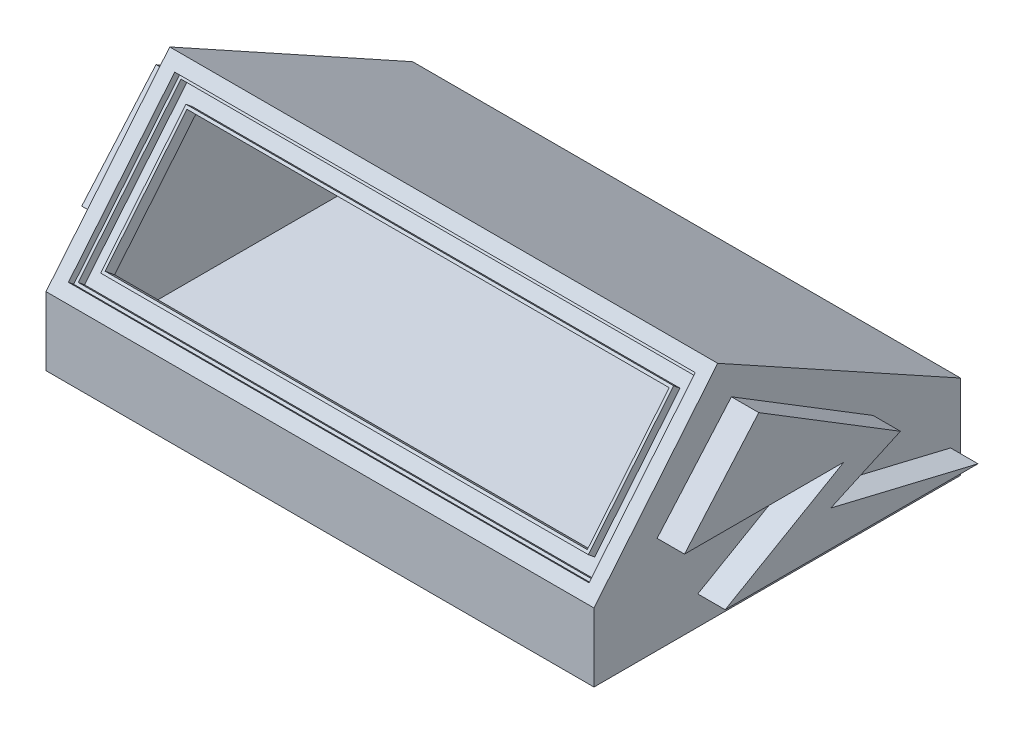
SolidWorks part; units mm, degrees
ref_plane "Front Plane" through (0, 0, 0) normal (0, 0, 1) x (1, 0, 0)
ref_plane "Top Plane" through (0, 0, 0) normal (0, 1, 0) x (1, 0, 0)
ref_plane "Right Plane" through (0, 0, 0) normal (1, 0, 0) x (0, 0, -1)
sketch "Sketch1" plane through (0, 0, 0) normal (1, 0, 0) x (0, 0, -1)
  line L0 (42.0739, 65.0414) -> (130.7147, 16.0632)
  line L5 (130.7147, 16.0632) -> (130.7147, -14.7157)
  line L6 (-4.3853, -14.7157) -> (164.6147, -14.7157) construction
  line L7 (130.7147, -14.7157) -> (-3.084, -14.7157)
  line L13 (-3.084, 10.2843) -> (-3.084, -14.7157)
  line L14 (-3.084, 10.2843) -> (42.0739, 65.0414)
  point P0 (0, 0)
extrude "Boss-Extrude2" add sketch "Sketch1" along normal mid plane 200
sketch "Sketch6" plane through (-100, 0, 0) normal (-1, 0, 0) x (0, 0, 1)
  line L0 (-99.8291, 20.1495) -> (-46.9657, 52.6082)
  line L5 (-46.9657, 52.6082) -> (-18.8617, 20.2843) construction
  line L6 (-99.8291, 20.1495) -> (-46.9657, 52.6082) construction
  line L7 (-46.9657, 52.6082) -> (-18.8617, 20.2843)
  line L8 (-18.8617, 20.2843) -> (-76.2365, 20.2843)
  line L9 (-76.2365, 20.2843) -> (-32.9353, -4.7157)
  line L10 (-32.9353, -4.7157) -> (-131.3101, -4.7157)
  line L11 (-131.3101, -4.7157) -> (-74.8772, 8.8048) construction
  line L12 (-32.9353, -4.7157) -> (-131.3101, -4.7157) construction
  line L13 (-131.3101, -4.7157) -> (-74.8772, 8.8048)
  line L14 (-74.8772, 8.8048) -> (-99.8291, 20.1495) construction
  line L15 (-74.8772, 8.8048) -> (-99.8291, 20.1495)
  line L16 (-73.3455, 8.6576) -> (-98.7661, 20.2154)
  line L17 (-98.7661, 20.2154) -> (-47.0651, 51.9604)
  line L18 (-47.0651, 51.9604) -> (-19.959, 20.7843)
  line L19 (-19.959, 20.7843) -> (-78.1025, 20.7843)
  line L20 (-78.1025, 20.7843) -> (-34.8013, -4.2157)
  line L21 (-34.8013, -4.2157) -> (-127.0772, -4.2157)
  line L22 (-127.0772, -4.2157) -> (-73.3455, 8.6576)
  point P0 (-63.3626, 19.2467)
  dimension "D1" = 0.5
extrude "Boss-Extrude4" add sketch "Sketch6" along normal blind 10 contours L16 L17 L18 L19 L20 L21 L22
mirror "Mirror1" about plane through (0, 0, 0) normal (1, 0, 0) of "Boss-Extrude4"
sketch "Sketch3" plane through (0, 0, 0) normal (1, 0, 0) x (0, 0, -1)
  line L10 (43.7761, 56.1034) -> (3.916, 7.7702)
  line L11 (3.916, 7.7702) -> (3.916, -7.7157)
  line L12 (3.916, -7.7157) -> (123.7147, -7.7157)
  line L13 (123.7147, -7.7157) -> (123.7147, 11.9335)
  line L14 (123.7147, 11.9335) -> (43.7761, 56.1034)
  line L15 (43.7761, 56.1034) -> (3.916, 7.7702)
  line L16 (3.916, 7.7702) -> (3.916, -7.7157)
  line L17 (3.916, -7.7157) -> (123.7147, -7.7157)
  line L18 (123.7147, -7.7157) -> (123.7147, 11.9335)
  line L19 (123.7147, 11.9335) -> (43.7761, 56.1034)
  dimension "D1" = 7
extrude "Cut-Extrude2" cut sketch "Sketch3" against normal mid plane 190 contours L15 L16 L17 L18 L19
sketch "Sketch4" plane through (0, 5.6769, 6.8837) normal (0, 0.6362, 0.7715) x (1, 0, 0)
  line L8 (-95, 71.9479) -> (-95, 10.9721)
  line L9 (-95, 10.9721) -> (95, 10.9721)
  line L10 (95, 10.9721) -> (95, 71.9479)
  line L11 (95, 71.9479) -> (-95, 71.9479)
  line L12 (-95, 71.9479) -> (-95, 10.9721)
  line L13 (-95, 10.9721) -> (95, 10.9721)
  line L14 (95, 10.9721) -> (95, 71.9479)
  line L15 (95, 71.9479) -> (-95, 71.9479)
  dimension "D1" = 5
extrude "Cut-Extrude3" cut sketch "Sketch4" against normal blind 2.5
sketch "Sketch5" plane through (0, 4.0863, 4.9549) normal (0, 0.6362, 0.7715) x (1, 0, 0)
  line L68 (88, 17.9721) -> (88, 64.9479)
  line L69 (-88, 17.9721) -> (88, 17.9721)
  line L70 (-88, 64.9479) -> (-88, 17.9721)
  line L71 (88, 64.9479) -> (-88, 64.9479)
  line L72 (88, 17.9721) -> (88, 64.9479)
  line L73 (-88, 17.9721) -> (88, 17.9721)
  line L74 (-88, 64.9479) -> (-88, 17.9721)
  line L75 (88, 64.9479) -> (-88, 64.9479)
  dimension "D1" = 7
extrude "Cut-Extrude4" cut sketch "Sketch5" against normal up to surface (4.5 mm away) up to face at (0, 31.9368, -23.8461)
sketch "Sketch8" plane through (0, 4.0863, 4.9549) normal (0, 0.6362, 0.7715) x (1, 0, 0)
  line L11 (94, 11.9721) -> (94, 70.9479)
  line L12 (89, 16.9721) -> (89, 65.9479)
  line L13 (-89, 16.9721) -> (89, 16.9721)
  line L14 (-89, 65.9479) -> (-89, 16.9721)
  line L15 (89, 65.9479) -> (-89, 65.9479)
  line L16 (89, 16.9721) -> (89, 65.9479)
  line L17 (-89, 16.9721) -> (89, 16.9721)
  line L18 (-89, 65.9479) -> (-89, 16.9721)
  line L19 (89, 65.9479) -> (-89, 65.9479)
  line L20 (-94, 11.9721) -> (94, 11.9721)
  line L21 (94, 70.9479) -> (-94, 70.9479)
  line L22 (-94, 70.9479) -> (-94, 11.9721)
  line L23 (94, 11.9721) -> (94, 70.9479)
  line L24 (-94, 11.9721) -> (94, 11.9721)
  line L25 (94, 70.9479) -> (-94, 70.9479)
  line L26 (-94, 70.9479) -> (-94, 11.9721)
  dimension "D1" = 1
  dimension "D2" = 1
extrude "Cut-Extrude5" cut sketch "Sketch8" against normal blind 3
